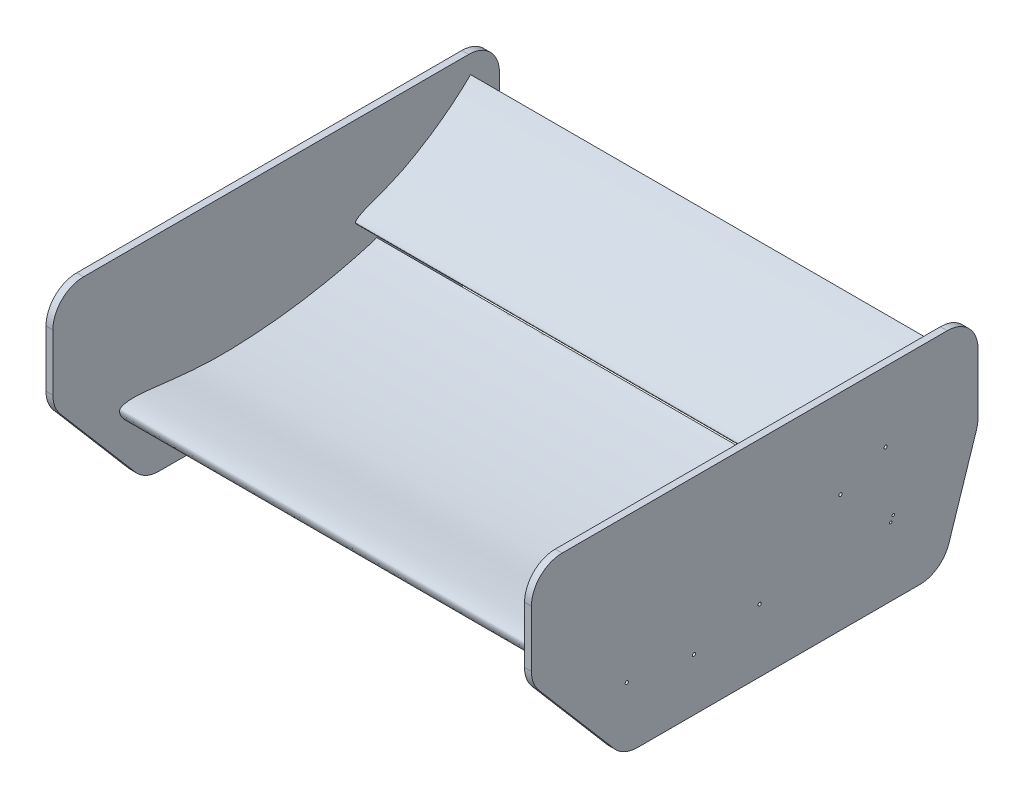
SolidWorks part; units mm, degrees
ref_plane "Front Plane" through (0, 0, 0) normal (0, 0, 1) x (1, 0, 0)
ref_plane "Top Plane" through (0, 0, 0) normal (0, 1, 0) x (1, 0, 0)
ref_plane "Right Plane" through (0, 0, 0) normal (1, 0, 0) x (0, 0, -1)
ref_plane "Soft Top Limit" through (0, 1174.6, 0) normal (0, 1, 0) x (1, 0, 0)
ref_plane "Soft Rear Limit" through (0, 0, -1192.975) normal (0, 0, 1) x (1, 0, 0)
ref_plane "Soft Right Limit" through (-501.65, 0, 0) normal (1, 0, 0) x (0, 0, -1)
ref_plane "Soft Left Limit" through (501.65, 0, 0) normal (1, 0, 0) x (0, 0, -1)
ref_plane "Soft Front Limit" through (0, 0, -165.1) normal (0, 0, 1) x (1, 0, 0)
ref_plane "Slant Limit" through (0, 528.6251, -619.2711) normal (0, -0.6492, 0.7606) x (1, 0, 0)
ref_plane "Bottom" through (0, 476.25, 0) normal (0, 1, 0) x (1, 0, 0)
ref_plane "Midplane" through (0, 0, 0) normal (1, 0, 0) x (0, 0, -1)
curve "Imported Airfoil Curve"
  spline degree 3 poles (0, 2520.0207, 6.126) (0, 2544.889, -1.81) (0, 2521.8965, 7.8839) (0, 2505.3253, 17.7145) (0, 2467.7144, 38.5723) (0, 2424.2142, 62.3813) (0, 2368.0949, 87.8078) (0, 2301.3729, 113.3478) (0, 2223.8362, 140.5377) (0, 2136.6129, 169.2441) (0, 2040.932, 199.097) (0, 1938.2341, 229.6055) (0, 1829.9414, 260.0781) (0, 1717.5266, 289.8586) (0, 1602.4273, 318.1375) (0, 1486.0259, 343.9752) (0, 1369.6902, 366.5754) (0, 1254.3666, 384.7865) (0, 1140.5393, 397.0034) (0, 1028.6357, 403.0127) (0, 919.0585, 402.9406) (0, 812.3986, 397.0375) (0, 709.2785, 385.5985) (0, 610.4299, 369.039) (0, 516.5862, 348.1086) (0, 428.5874, 323.3415) (0, 347.2653, 295.2055) (0, 273.332, 264.2656) (0, 207.4209, 231.0894) (0, 150.0337, 196.3024) (0, 101.596, 160.572) (0, 62.3674, 124.65) (0, 32.4977, 89.3959) (0, 12.0597, 55.6746) (0, 1.683, 26.6201) (0, -0.5567, 6.5526) (0, 0.5894, -3.9947) (0, 1.6947, -9.1451) (0, 2.8711, -12.4915) (0, 3.9449, -14.9776) (0, 4.8993, -16.669) (0, 5.9763, -18.2433) (0, 7.3264, -19.6365) (0, 8.8595, -20.9434) (0, 11.1868, -22.7306) (0, 14.6073, -24.7406) (0, 20.085, -27.4067) (0, 26.8353, -29.9257) (0, 44.6446, -35.1819) (0, 77.8093, -38.8998) (0, 130.2841, -38.2927) (0, 196.3018, -31.4611) (0, 276.2192, -18.4434) (0, 370.8288, 0.8611) (0, 480.7331, 24.811) (0, 605.9792, 50.0099) (0, 745.0759, 74.1542) (0, 895.4497, 95.0846) (0, 1053.6786, 110.004) (0, 1215.6439, 118.3392) (0, 1377.6893, 121.6348) (0, 1537.1174, 120.5125) (0, 1691.5141, 115.2051) (0, 1838.3121, 105.7388) (0, 1975.028, 93.0069) (0, 2099.5942, 78.4581) (0, 2210.5746, 63.1262) (0, 2306.3634, 48.0168) (0, 2387.2069, 33.7158) (0, 2449.0745, 22.0129) (0, 2499.1865, 10.4993) (0, 2520.0207, 6.126) (0, 2544.889, -1.81) (0, 2521.8965, 7.8839) knots -0.016237 -0.007308 -0.001841 0 0.001813 0.006911 0.014576 0.024172 0.035572 0.049013 0.064513 0.081849 0.100772 0.120997 0.142228 0.164173 0.186537 0.209023 0.231367 0.25332 0.274804 0.295858 0.316449 0.336531 0.356033 0.374893 0.39299 0.410197 0.426388 0.441459 0.455334 0.467938 0.479236 0.489204 0.497851 0.505194 0.511308 0.515097 0.516441 0.517273 0.51806 0.518436 0.518797 0.519154 0.519508 0.519887 0.520289 0.52116 0.522116 0.52372 0.525214 0.532575 0.542381 0.554776 0.569931 0.588005 0.609188 0.633329 0.660001 0.688743 0.718873 0.749543 0.780127 0.810209 0.839387 0.867183 0.893104 0.91676 0.937874 0.956199 0.971544 0.983763 0.992692 0.998159 1 1.001813 1.006911 1.014576 periodic
sketch "Airfoils Sketch" plane through (0, 0, 0) normal (1, 0, 0) x (0, 0, -1)
  line L0 (165.1, 1174.6) -> (165.1, 1060.6753) construction
  line L1 (165.1, 1060.6753) -> (663.9798, 476.25) construction
  line L2 (663.9798, 476.25) -> (1192.975, 476.25) construction
  line L3 (1192.975, 476.25) -> (1192.975, 1174.6) construction
  line L4 (1192.975, 1174.6) -> (165.1, 1174.6) construction
  line L5 (509.9361, 1174.6) -> (-509.9361, 1174.6) construction
  line L6 (165.1, 67.0076) -> (165.1, -67.0076) construction
  line L7 (364.7288, 826.8151) -> (873.8134, 230.4351) construction
  line L8 (279.3831, 476.25) -> (-279.3831, 476.25) construction
  line L9 (1192.975, 353.2696) -> (1192.975, -353.2696) construction
  line L10 (414.7055, 818.0274) -> (401.202, 972.3726) construction
  line L11 (945.202, 874.5029) -> (933.446, 1008.8748) construction
  line L12 (939.324, 941.6889) -> (407.9538, 895.2) construction
  line L13 (306.3538, 895.2) -> (1192.975, 895.2) construction
  line L14 (866.0383, 1036.8746) -> (926.5682, 940.0065) construction
  line L15 (1102.685, 1185.4108) -> (1163.8108, 1087.5892) construction
  line L16 (1133.2479, 1136.5) -> (896.3033, 988.4406) construction
  line L21 (176.2614, 1047.6) -> (1192.975, 1047.6) construction
  spline S0 degree 3 poles (935.2529, 940.0507) (940.3147, 942.1548) (935.6767, 939.7163) (932.3848, 937.3638) (924.8872, 932.3286) (916.21, 926.5709) (904.9213, 920.2497) (891.4161, 913.7156) (875.6775, 906.6433) (857.9391, 899.0809) (838.4515, 891.1278) (817.5075, 882.9123) (795.3921, 874.6046) (772.4019, 866.3681) (748.8232, 858.3979) (724.9284, 850.9153) (700.9897, 844.1113) (677.1845, 838.2437) (653.5854, 833.657) (630.2782, 830.4035) (607.3492, 828.4639) (584.9266, 827.7965) (563.1459, 828.3505) (542.1676, 830.0521) (522.1586, 832.7575) (503.3041, 836.37) (485.7865, 840.8065) (469.765, 845.9615) (455.382, 851.7275) (442.7539, 857.9825) (431.9816, 864.5947) (423.1327, 871.4111) (416.2539, 878.2548) (411.376, 884.946) (408.6865, 890.8402) (407.8599, 894.9991) (407.9116, 897.2265) (408.051, 898.3239) (408.2374, 899.0451) (408.4178, 899.5844) (408.5873, 899.9553) (408.7846, 900.3039) (409.0422, 900.6195) (409.3397, 900.9203) (409.7947, 901.3358) (410.4746, 901.8174) (411.5732, 902.4729) (412.9407, 903.1204) (416.5733, 904.5379) (423.4463, 905.9074) (434.4368, 906.7165) (448.3721, 906.4646) (465.3261, 905.1664) (485.4664, 902.8148) (508.8897, 899.7641) (535.5455, 896.7257) (565.0805, 894.155) (596.9177, 892.4579) (630.2914, 892.1587) (664.3294, 893.3038) (698.2942, 895.5048) (731.6326, 898.5836) (763.8436, 902.4482) (794.3904, 907.0475) (822.7695, 912.1503) (848.5739, 917.4165) (871.5218, 922.6042) (891.2949, 927.4743) (907.9553, 931.9087) (920.6916, 935.461) (930.9716, 938.764) (935.2529, 940.0507) (940.3147, 942.1548) (935.6767, 939.7163) knots -0.016237 -0.007308 -0.001841 0 0.001813 0.006911 0.014576 0.024172 0.035572 0.049013 0.064513 0.081849 0.100772 0.120997 0.142228 0.164173 0.186537 0.209023 0.231367 0.25332 0.274804 0.295858 0.316449 0.336531 0.356033 0.374893 0.39299 0.410197 0.426388 0.441459 0.455334 0.467938 0.479236 0.489204 0.497851 0.505194 0.511308 0.515097 0.516441 0.517273 0.51806 0.518436 0.518797 0.519154 0.519508 0.519887 0.520289 0.52116 0.522116 0.52372 0.525214 0.532575 0.542381 0.554776 0.569931 0.588005 0.609188 0.633329 0.660001 0.688743 0.718873 0.749543 0.780127 0.810209 0.839387 0.867183 0.893104 0.91676 0.937874 0.956199 0.971544 0.983763 0.992692 0.998159 1 1.001813 1.006911 1.014576 only from (939.324, 941.6889) to (939.324, 941.6889)
  spline S1 degree 3 poles (1131.7374, 1134.7673) (1133.5995, 1136.953) (1132.0147, 1134.712) (1131.0377, 1132.8312) (1128.7359, 1128.6983) (1126.0553, 1123.9476) (1122.2899, 1118.3128) (1117.5406, 1112.0516) (1111.8769, 1105.0082) (1105.3965, 1097.2604) (1098.1926, 1088.9143) (1090.3713, 1080.0994) (1082.0253, 1070.9629) (1073.254, 1061.6516) (1064.1447, 1052.3247) (1054.7721, 1043.1501) (1045.2175, 1034.2818) (1035.5025, 1025.8823) (1025.5791, 1018.1297) (1015.4749, 1011.0686) (1005.2348, 1004.7108) (994.9285, 999.0671) (984.6313, 994.1461) (974.4357, 989.9515) (964.4538, 986.456) (954.795, 983.6583) (945.5642, 981.5631) (936.8608, 980.159) (928.7768, 979.4298) (921.3956, 979.3461) (914.7955, 979.8704) (909.0446, 980.9475) (904.2067, 982.5058) (900.3389, 984.4687) (897.682, 986.58) (896.3072, 988.3245) (895.8017, 989.3763) (895.6058, 989.9216) (895.5213, 990.3026) (895.4772, 990.5972) (895.4681, 990.8106) (895.4773, 991.0202) (895.5225, 991.2288) (895.5898, 991.4399) (895.7034, 991.742) (895.9061, 992.1285) (896.263, 992.6957) (896.7472, 993.3231) (898.1055, 994.8485) (900.9876, 997.1221) (905.9247, 1000.1133) (912.4884, 1003.3096) (920.7099, 1006.7355) (930.6689, 1010.4274) (942.3265, 1014.5737) (955.4898, 1019.4945) (969.8856, 1025.3183) (985.1482, 1032.0973) (1000.7954, 1039.894) (1016.4092, 1048.5229) (1031.7378, 1057.6271) (1046.5653, 1066.992) (1060.6797, 1076.4556) (1073.8427, 1085.8664) (1085.8742, 1094.9966) (1096.6653, 1103.5909) (1106.1418, 1111.4691) (1114.2121, 1118.4443) (1120.9333, 1124.4758) (1126.0328, 1129.1625) (1130.0452, 1133.1487) (1131.7374, 1134.7673) (1133.5995, 1136.953) (1132.0147, 1134.712) knots -0.016237 -0.007308 -0.001841 0 0.001813 0.006911 0.014576 0.024172 0.035572 0.049013 0.064513 0.081849 0.100772 0.120997 0.142228 0.164173 0.186537 0.209023 0.231367 0.25332 0.274804 0.295858 0.316449 0.336531 0.356033 0.374893 0.39299 0.410197 0.426388 0.441459 0.455334 0.467938 0.479236 0.489204 0.497851 0.505194 0.511308 0.515097 0.516441 0.517273 0.51806 0.518436 0.518797 0.519154 0.519508 0.519887 0.520289 0.52116 0.522116 0.52372 0.525214 0.532575 0.542381 0.554776 0.569931 0.588005 0.609188 0.633329 0.660001 0.688743 0.718873 0.749543 0.780127 0.810209 0.839387 0.867183 0.893104 0.91676 0.937874 0.956199 0.971544 0.983763 0.992692 0.998159 1 1.001813 1.006911 1.014576 only from (1133.2479, 1136.5) to (1133.2479, 1136.5)
  dimension "D1" = 533.4
  dimension "D2" = 279.4
  dimension "D3" = 5
  dimension "D4" = 101.6
  dimension "D5" = 279.4
  dimension "D6" = 38.1
  dimension "D7" = 32
  dimension "D8" = 59.7271
  dimension "D9" = 127
extrude "Extruded Airfoils" add sketch "Airfoils Sketch" along normal offset from surface (487.45 mm away) 14.2 up to plane "Soft Left Limit"
sketch "Endplate Sketch" plane through (501.65, 0, 0) normal (1, 0, 0) x (0, 0, -1)
  line L6 (333.4477, 1174.6) -> (1129.475, 1174.6)
  line L7 (1192.975, 1174.6) -> (165.1, 1174.6) construction
  line L8 (1192.975, 1111.1) -> (1192.975, 986.6717)
  line L9 (1192.975, 476.25) -> (1192.975, 1174.6) construction
  line L11 (1189.8464, 966.9854) -> (1132.8969, 792.34)
  line L12 (1072.5255, 748.5263) -> (489.1772, 748.5263)
  line L19 (440.8805, 770.7991) -> (285.151, 953.2323)
  line L26 (269.9477, 994.4595) -> (269.9477, 1111.1)
  line L28 (165.1, 1060.6753) -> (663.9798, 476.25) construction
  arc A12 (1129.475, 1174.6) -> (1192.975, 1111.1) centre (1129.475, 1111.1) cw
  arc A13 (1192.975, 986.6717) -> (1189.8464, 966.9854) centre (1129.475, 986.6717) cw
  arc A14 (1132.8969, 792.34) -> (1072.5255, 748.5263) centre (1072.5255, 812.0263) cw
  arc A15 (489.1772, 748.5263) -> (440.8805, 770.7991) centre (489.1772, 812.0263) cw
  arc A16 (285.151, 953.2323) -> (269.9477, 994.4595) centre (333.4477, 994.4595) cw
  arc A17 (333.4477, 1174.6) -> (269.9477, 1111.1) centre (333.4477, 1111.1) ccw
  point P16 (1192.975, 1174.6)
  point P19 (1192.975, 976.5799)
  point P29 (269.9477, 1174.6)
  dimension "D1" = 63.5
extrude "Extruded Endplate" add sketch "Endplate Sketch" against normal up to surface (14.2 mm away)
mirror "Mirror" about plane through (0, 0, 0) normal (1, 0, 0) of bodies 106
sketch "Sketch1" plane through (501.65, 0, 0) normal (1, 0, 0) x (0, 0, -1)
  circle A0 centre (466.9636, 876.0274) radius 3.302
extrude "Cut-Extrude1" cut sketch "Sketch1" against normal up to surface (14.2 mm away) up to face at (487.45, 961.8886, -750.0842)
sketch "Sketch2" plane through (501.65, 0, 0) normal (1, 0, 0) x (0, 0, -1)
  circle A0 centre (605.9718, 856.7319) radius 3.302
extrude "Cut-Extrude2" cut sketch "Sketch2" against normal up to surface (14.2 mm away) up to face at (487.45, 961.8886, -750.0842)
sketch "Sketch3" plane through (501.65, 0, 0) normal (1, 0, 0) x (0, 0, -1)
  circle A0 centre (741.5917, 878.9853) radius 3.302
  circle A1 centre (908.6976, 991.5292) radius 3.302
  circle A2 centre (1002.03, 1029.97) radius 3.302
extrude "Cut-Extrude3" cut sketch "Sketch3" against normal up to surface (14.2 mm away) up to face at (487.45, 961.8886, -750.0842)
sketch "Sketch4" plane through (501.65, 0, 0) normal (1, 0, 0) x (0, 0, -1)
  circle A0 centre (1018.0658, 900.3059) radius 2.54
  circle A1 centre (1012.4254, 889.9969) radius 2.54
extrude "Cut-Extrude4" cut sketch "Sketch4" against normal up to surface (14.2 mm away) up to face at (487.45, 961.8886, -750.0842)
sketch "Sketch5" plane through (-485.164, 0, 0) normal (1, 0, 0) x (0, 0, -1)
  circle A0 centre (763.2383, 814.1335) radius 3.2766 construction
  circle A1 centre (763.2383, 849.0585) radius 3.2766 construction
  circle A2 centre (763.2383, 814.1335) radius 3.2766
  circle A3 centre (763.2383, 849.0585) radius 3.2766
extrude "Cut-Extrude5" cut sketch "Sketch5" against normal through all
sketch "Sketch6" plane through (0, 0, 0) normal (0, 1, 0) x (1, 0, 0)
  line L0 (-353.9817, 49.2941) -> (-313.6336, 233.8042)
  line L1 (-313.6336, 233.8042) -> (-299.4255, 425.6563)
  line L2 (-299.4255, 425.6563) -> (-299.4255, 549.876)
  line L3 (-299.4255, 549.876) -> (-249.9357, 633.966)
  line L4 (-249.9357, 633.966) -> (-249.9357, 740.1366)
  line L5 (-249.9357, 740.1366) -> (-226.6315, 828.1612)
  line L6 (-226.6315, 828.1612) -> (-178.4697, 895.4711)
  line L9 (144.7205, 1337.384) -> (837.9513, 1337.384)
  line L10 (837.9513, 1337.384) -> (815.4478, 49.2941)
  line L11 (815.4478, 49.2941) -> (-353.9817, 49.2941)
  line L12 (-487.45, 895.4711) -> (487.45, 895.4711) construction
  line L13 (-178.4697, 895.4711) -> (0, 923.101)
  line L14 (0, 923.101) -> (69.2002, 974.8864)
  line L15 (69.2002, 974.8864) -> (95.0928, 1059.0376)
  line L16 (95.0928, 1059.0376) -> (95.0928, 1240.2864)
  line L17 (95.0928, 1240.2864) -> (144.7205, 1337.384)
extrude "Cut-Extrude6" [suppressed] cut sketch "Sketch6" against normal through all both and the other way through all
